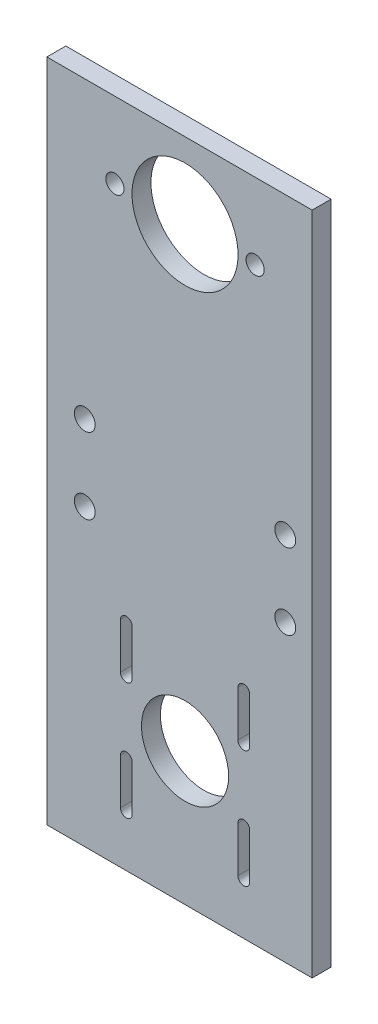
SolidWorks part; units mm, degrees
ref_plane "Front Plane" through (0, 0, 0) normal (0, 0, 1) x (1, 0, 0)
ref_plane "Top Plane" through (0, 0, 0) normal (0, 1, 0) x (1, 0, 0)
ref_plane "Right Plane" through (0, 0, 0) normal (1, 0, 0) x (0, 0, -1)
sketch "Sketch1" plane through (0, 0, 0) normal (0, 0, 1) x (1, 0, 0)
  line L0 (-26.4505, -10) -> (26.4505, 10) construction
  line L2 (-36.4505, -87.7468) -> (-36.4505, 87.7468)
  line L3 (-36.4505, 87.7468) -> (33.5495, 87.7468)
  line L4 (33.5495, -87.7468) -> (33.5495, 87.7468)
  line L5 (-26.4505, 10) -> (26.4505, -10) construction
  line L6 (-36.4505, -87.7468) -> (33.5495, -87.7468)
  line L7 (-18.5, 67.7468) -> (18.5, 67.7468) construction
  line L8 (-15.5, -31.1434) -> (-15.5, -43.1434) construction
  line L9 (-15.5, -68.1434) -> (15.5, -68.1434) construction
  line L11 (-15.5, -68.1434) -> (-15.5, -37.1434) construction
  line L14 (-15.5, -37.1434) -> (15.5, -37.1434) construction
  line L15 (15.5, -68.1434) -> (15.5, -37.1434) construction
  line L16 (-15.5, -68.1434) -> (15.5, -37.1434) construction
  line L17 (-15.5, -37.1434) -> (15.5, -68.1434) construction
  line L18 (-13.95, -31.1434) -> (-13.95, -43.1434)
  line L19 (-17.05, -31.1434) -> (-17.05, -43.1434)
  line L20 (15.5, -31.1434) -> (15.5, -43.1434) construction
  line L21 (17.05, -31.1434) -> (17.05, -43.1434)
  line L22 (13.95, -31.1434) -> (13.95, -43.1434)
  line L23 (15.5, -62.1434) -> (15.5, -74.1434) construction
  line L24 (17.05, -62.1434) -> (17.05, -74.1434)
  line L25 (13.95, -62.1434) -> (13.95, -74.1434)
  line L26 (-15.5, -62.1434) -> (-15.5, -74.1434) construction
  line L27 (-13.95, -62.1434) -> (-13.95, -74.1434)
  line L28 (-17.05, -62.1434) -> (-17.05, -74.1434)
  circle A0 centre (-18.5, 67.7468) radius 2.4
  circle A1 centre (18.5, 67.7468) radius 2.4
  circle A2 centre (0, 67.7468) radius 5
  circle A3 centre (-26.4505, 10) radius 2.75
  circle A4 centre (26.4505, 10) radius 2.75
  circle A5 centre (26.4505, -10) radius 2.75
  circle A6 centre (-26.4505, -10) radius 2.75
  circle A7 centre (0, 67.7468) radius 14
  circle A12 centre (0, -52.6434) radius 11.5
  arc A13 (-13.95, -31.1434) -> (-17.05, -31.1434) centre (-15.5, -31.1434) ccw
  arc A14 (-17.05, -43.1434) -> (-13.95, -43.1434) centre (-15.5, -43.1434) ccw
  arc A15 (17.05, -31.1434) -> (13.95, -31.1434) centre (15.5, -31.1434) ccw
  arc A16 (13.95, -43.1434) -> (17.05, -43.1434) centre (15.5, -43.1434) ccw
  arc A17 (17.05, -62.1434) -> (13.95, -62.1434) centre (15.5, -62.1434) ccw
  arc A18 (13.95, -74.1434) -> (17.05, -74.1434) centre (15.5, -74.1434) ccw
  arc A19 (-13.95, -62.1434) -> (-17.05, -62.1434) centre (-15.5, -62.1434) ccw
  arc A20 (-17.05, -74.1434) -> (-13.95, -74.1434) centre (-15.5, -74.1434) ccw
  point P0 (0, 0)
  point P5 (-36.4505, 0)
  point P6 (0, -52.6434)
  point P25 (-15.5, -37.1434)
  point P38 (15.5, -37.1434)
  point P45 (15.5, -68.1434)
  point P52 (-15.5, -68.1434)
  point P64 (0, 0)
  point P65 (0, 0)
  point P66 (0, 0)
  dimension "D4" = 4.8
  dimension "D5" = 10
  dimension "D6" = 5.5
  dimension "D11" = 28
  dimension "D7" = 23
  dimension "D12" = 1.55
  dimension "D1" = 70
  dimension "D2" = 31
  dimension "D3" = 37
  dimension "D8" = 20
  dimension "D9" = 12
  dimension "D10" = 20
extrude "Boss-Extrude1" add sketch "Sketch1" along normal blind 5 contours L2 L6 L4 L3 A7 A6 A5 A4 A3 A1 A0 region at (-1.6283, -1.1763, 0)
